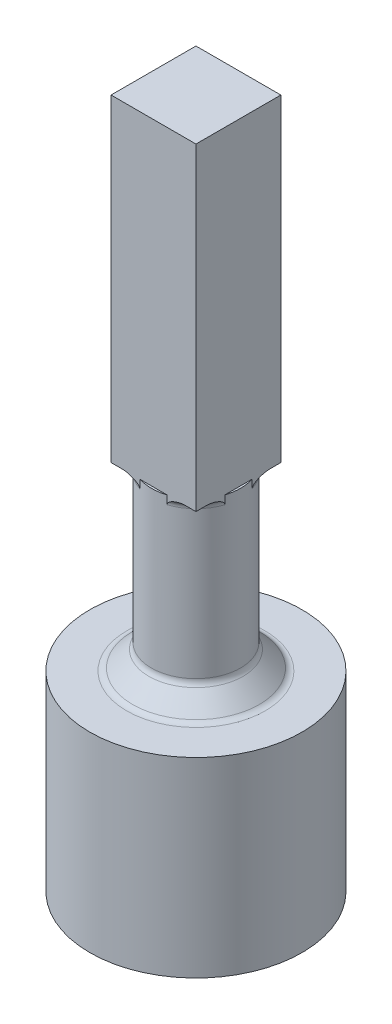
SolidWorks part; units mm, degrees
ref_plane "Front Plane" through (0, 0, 0) normal (0, 0, 1) x (1, 0, 0)
ref_plane "Top Plane" through (0, 0, 0) normal (0, 1, 0) x (1, 0, 0)
ref_plane "Right Plane" through (0, 0, 0) normal (1, 0, 0) x (0, 0, -1)
sketch "Sketch1" plane through (0, 0, 0) normal (0, 1, 0) x (1, 0, 0)
  line L1 (-3.3, 2.55) -> (3.3, 2.55)
  line L2 (-3.3, 2.55) -> (-3.3, -2.55)
  line L3 (-3.3, -2.55) -> (3.3, -2.55)
  line L4 (3.3, 2.55) -> (3.3, -2.55)
  line L5 (-3.3, 2.55) -> (3.3, -2.55) construction
  line L6 (-3.3, -2.55) -> (3.3, 2.55) construction
  circle A1 centre (0, 0) radius 5
  dimension "D2" = 10
  dimension "D1" = 5.1
  dimension "D3" = 6.6
extrude "Boss-Extrude1" add sketch "Sketch1" along normal blind 5
sketch "Sketch2" plane through (0, 5, 0) normal (0, 1, 0) x (1, 0, 0)
  circle A0 centre (0, 0) radius 5
  dimension "D1" = 10
extrude "Boss-Extrude2" add sketch "Sketch2" along normal blind 4
sketch "Sketch3" plane through (0, 9, 0) normal (0, 1, 0) x (1, 0, 0)
  circle A0 centre (0, 0) radius 2.1
  dimension "D1" = 4.2
extrude "Boss-Extrude3" add sketch "Sketch3" along normal blind 8.5
sketch "Sketch4" plane through (0, 17.5, 0) normal (0, 1, 0) x (1, 0, 0)
  line L1 (-2, -2) -> (2, -2)
  line L2 (-2, -2) -> (-2, 2)
  line L3 (-2, 2) -> (2, 2)
  line L4 (2, -2) -> (2, 2)
  line L5 (-2, -2) -> (2, 2) construction
  line L6 (-2, 2) -> (2, -2) construction
  point P0 (0, 0)
  dimension "D1" = 4
extrude "Boss-Extrude4" add sketch "Sketch4" along normal blind 15
chamfer "Chamfer1" distance 1 angle 45 1 edges at (0, 9, 2.1)
fillet "Fillet1" radius 0.4 6 edges at (-1.4849, 17.5, 1.4849) (-1.4849, 17.5, -1.4849) (1.4849, 17.5, -1.4849) (1.4849, 17.5, 1.4849) (0, 10, 2.1) (0, 9, 3.1)
